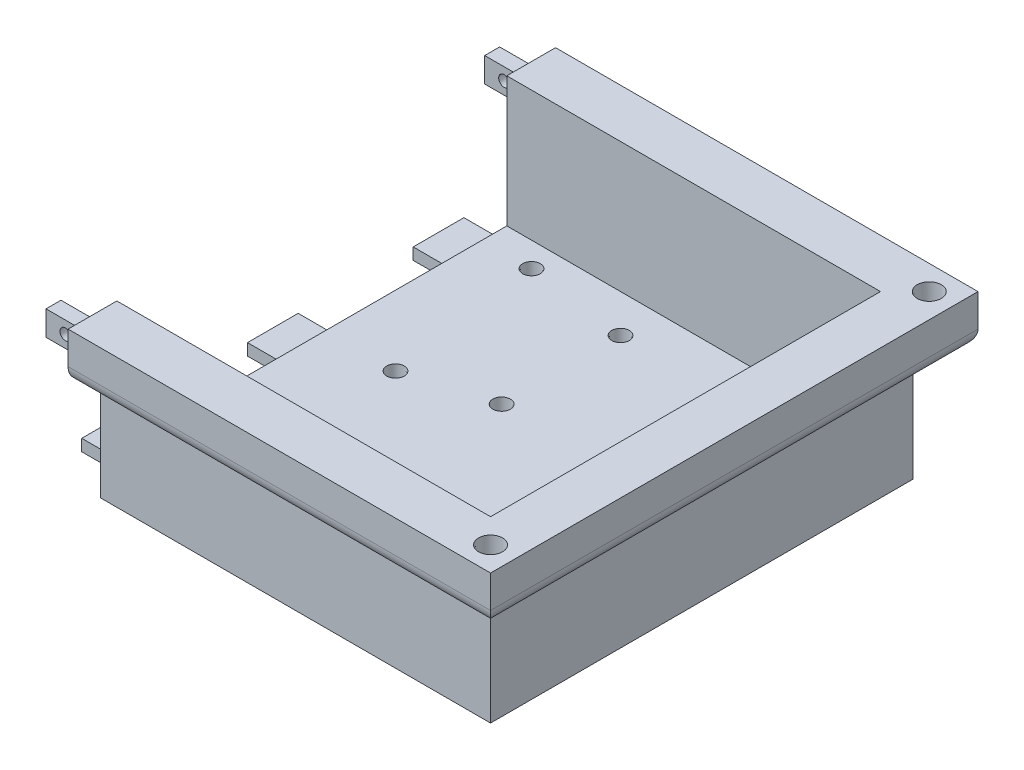
SolidWorks part; units mm, degrees
ref_plane "Front Plane" through (0, 0, 0) normal (0, 0, 1) x (1, 0, 0)
ref_plane "Top Plane" through (0, 0, 0) normal (0, 1, 0) x (1, 0, 0)
ref_plane "Right Plane" through (0, 0, 0) normal (1, 0, 0) x (0, 0, -1)
sketch "Sketch1" plane through (0, 0, 0) normal (0, 1, 0) x (1, 0, 0)
  line L1 (-102.5, 65) -> (102.5, 65)
  line L2 (-102.5, 65) -> (-102.5, -65)
  line L3 (-102.5, -65) -> (102.5, -65)
  line L4 (102.5, 65) -> (102.5, -65)
  line L5 (-102.5, 65) -> (102.5, -65) construction
  line L6 (-102.5, -65) -> (102.5, 65) construction
  point P0 (0, 0)
  dimension "D1" = 130
  dimension "D2" = 205
extrude "Boss-Extrude1" add sketch "Sketch1" along normal blind 10
sketch "Sketch2" plane through (0, 10, 0) normal (0, 1, 0) x (1, 0, 0)
  line L11 (-102.5, 65) -> (102.5, 65)
  line L12 (-102.5, 65) -> (-102.5, -65)
  line L13 (-102.5, -65) -> (102.5, -65)
  line L14 (-97.5, -60) -> (97.5, -60)
  line L15 (97.5, -60) -> (97.5, 60)
  line L16 (-97.5, 60) -> (-97.5, -60)
  line L17 (97.5, 60) -> (-97.5, 60)
  line L18 (-97.5, -60) -> (97.5, -60)
  line L19 (97.5, -60) -> (97.5, 60)
  line L20 (-97.5, 60) -> (-97.5, -60)
  line L21 (97.5, 60) -> (-97.5, 60)
  line L22 (102.5, 65) -> (102.5, -65)
  dimension "D1" = 5
extrude "Boss-Extrude2" add sketch "Sketch2" along normal blind 40
sketch "Sketch3" plane through (0, 10, 0) normal (0, 1, 0) x (1, 0, 0)
  line L0 (-97.5, -60) -> (97.5, -60) construction
  line L1 (-92.5, -55) -> (-2.5, -55)
  line L2 (-92.5, -55) -> (-92.5, -2)
  line L3 (-92.5, -2) -> (-2.5, -2)
  line L4 (-2.5, -55) -> (-2.5, -2)
  line L5 (-84.35, -28.5) -> (-10.65, -28.5) construction
  line L6 (2.5, -2) -> (2.5, -55)
  line L7 (2.5, -55) -> (92.5, -55)
  line L8 (92.5, -55) -> (92.5, -2)
  line L9 (92.5, -2) -> (2.5, -2)
  line L10 (-97.5, 60) -> (-97.5, -60) construction
  line L13 (10.65, -28.5) -> (84.35, -28.5) construction
  circle A0 centre (-84.35, -28.5) radius 2.5
  circle A1 centre (-10.65, -28.5) radius 2.5
  point P4 (-47.5, -2)
  point P12 (-47.5, -28.5)
  point P13 (-92.5, -28.5)
  point P17 (84.35, -28.5)
  point P21 (10.65, -28.5)
  point P25 (2.5, -28.5)
  point P26 (47.5, -2)
  point P27 (47.5, -28.5)
  dimension "D5" = 5
  dimension "D1" = 90
  dimension "D2" = 53
  dimension "D3" = 5
  dimension "D4" = 73.7
  dimension "D6" = 90
  dimension "D7" = 53
  dimension "D8" = 5
  dimension "D9" = 5
  dimension "D10" = 73.7
sketch "Sketch6" plane through (-102.5, 0, 0) normal (-1, 0, 0) x (0, 0, 1)
  line L0 (-65, 50) -> (65, 50) construction
  line L1 (-60, 50) -> (0, 50)
  line L2 (-60, 50) -> (-60, 10)
  line L3 (-60, 10) -> (0, 10)
  line L4 (0, 50) -> (0, 10)
  line L5 (-60, 10) -> (60, 10) construction
extrude "Cut-Extrude1" cut sketch "Sketch6" against normal up to next
sketch "Sketch10" plane through (0, 10, 0) normal (0, 1, 0) x (1, 0, 0)
  line L1 (26, 51.5) -> (69, 51.5)
  line L2 (26, 51.5) -> (26, 8.5)
  line L3 (26, 8.5) -> (69, 8.5)
  line L4 (69, 51.5) -> (69, 8.5)
  line L6 (29.2, 48.3) -> (65.8, 48.3) construction
  line L7 (65.8, 48.3) -> (65.8, 11.7) construction
  line L8 (65.8, 11.7) -> (29.2, 11.7) construction
  line L9 (29.2, 11.7) -> (29.2, 48.3) construction
  line L12 (92.5, -2) -> (2.5, -2) construction
  line L13 (-102.5, 60) -> (-102.5, 0) construction
  point P8 (29.2, 48.3)
  point P9 (65.8, 48.3)
  point P10 (29.2, 11.7)
  point P11 (65.8, 11.7)
  point P14 (47.5, 48.3)
  point P17 (47.5, 8.5)
  point P18 (29.2, 30)
  point P19 (26, 30)
  point P20 (47.5, -2)
  point P21 (-102.5, 30)
  dimension "D1" = 43
  dimension "D2" = 43
  dimension "D5" = 36.6
sketch "Sketch9" plane through (0, 10, 0) normal (0, 1, 0) x (1, 0, 0)
  line L1 (-92.5, 55) -> (9.1, 55)
  line L2 (-92.5, 55) -> (-92.5, 1.7)
  line L3 (-92.5, 1.7) -> (9.1, 1.7)
  line L4 (9.1, 55) -> (9.1, 1.7)
  line L5 (97.5, 60) -> (-102.5, 60) construction
  line L7 (-97.5, 0) -> (-97.5, -60) construction
  point P8 (4.05, 4.2)
  point P9 (-26.4, 9.3)
  point P10 (-26.4, 37.2)
  point P11 (-2.3, 52.4)
  point P12 (-77.2, 52.4)
  point P13 (-78.5, 4.2)
  dimension "D1" = 101.6
  dimension "D2" = 53.3
  dimension "D3" = 5
  dimension "D4" = 2.5
  dimension "D5" = 14
  dimension "D6" = 1.3
  dimension "D7" = 50.8
  dimension "D8" = 24.1
  dimension "D9" = 27.9
  dimension "D10" = 15.2
  dimension "D11" = 5.1
  dimension "D12" = 82.55
  dimension "D13" = 5
hole_wizard "Hole1" positions "Sketch7" profile "Sketch8" legacy
sketch "Sketch7" plane through (0, 10, 0) normal (0, 1, 0) x (1, 0, 0)
  point P0 (-84.35, -28.5)
  point P3 (-10.65, -28.5)
  point P6 (-78.5, 4.2)
  point P9 (-77.2, 52.4)
  point P12 (-26.4, 9.3)
  point P15 (-26.4, 37.2)
  point P18 (-2.3, 52.4)
  point P21 (4.05, 4.2)
  point P25 (29.2, 48.3)
  point P28 (65.8, 48.3)
  point P31 (65.8, 11.7)
  point P34 (29.2, 11.7)
  point P38 (10.65, -28.5)
  point P41 (84.35, -28.5)
sketch "Sketch8" plane through (-84.35, 10, 28.5) normal (1, 0, 0) x (0, 0, 1)
  line L0 (0, 0) -> (0, 8)
  line L1 (0, 8) -> (2.4, 8)
  line L2 (2.4, 8) -> (2.4, 6)
  line L3 (2.4, 6) -> (2.7, 6)
  line L4 (2.7, 6) -> (2.7, 0)
  line L5 (2.7, 0) -> (0, 0)
  line L6 (0, 110) -> (0, -10) construction
  dimension "Diameter" = 4.8
  dimension "Depth" = 8
  dimension "C-Bore Diameter" = 5.4
  dimension "C-Bore Depth" = 6
chamfer "Chamfer1" distance 6 distance2 0.3 14 edges at (-84.35, 4, 31.2) (-10.65, 4, 31.2) (-2.3, 4, -49.7) (4.05, 4, -1.5) (-26.4, 4, -6.6) (-26.4, 4, -34.5) (-77.2, 4, -49.7) (-78.5, 4, -1.5) (65.8, 4, -45.6) (29.2, 4, -45.6) (29.2, 4, -9) (65.8, 4, -9) (84.35, 4, 31.2) (10.65, 4, 31.2) first distance on face at (-84.35, 4, 31.2) first distance on face at (-10.65, 4, 31.2) first distance on face at (-2.3, 4, -49.7) first distance on face at (4.05, 4, -1.5) first distance on face at (-26.4, 4, -6.6) first distance on face at (-26.4, 4, -34.5) first distance on face at (-77.2, 4, -49.7) first distance on face at (-78.5, 4, -1.5) first distance on face at (65.8, 4, -45.6) first distance on face at (29.2, 4, -45.6) first distance on face at (29.2, 4, -9) first distance on face at (65.8, 4, -9) first distance on face at (84.35, 4, 31.2) first distance on face at (10.65, 4, 31.2)
sketch "Sketch11" plane through (0, 50, 0) normal (0, 1, 0) x (1, 0, 0)
  line L0 (-112.5, 75) -> (112.5, 75)
  line L1 (112.5, 75) -> (112.5, -75)
  line L2 (112.5, -75) -> (-112.5, -75)
  line L3 (-112.5, -75) -> (-112.5, 0)
  line L4 (-112.5, 0) -> (-102.5, 0)
  line L5 (-102.5, 0) -> (-102.5, -65)
  line L6 (-102.5, -65) -> (102.5, -65)
  line L7 (102.5, -65) -> (102.5, 65)
  line L9 (-112.5, 60) -> (-112.5, 75)
  line L11 (-102.5, 60) -> (-112.5, 60)
  line L12 (-102.5, 60) -> (-102.5, 65)
  line L13 (-102.5, 65) -> (102.5, 65)
  dimension "D1" = 10
  dimension "D2" = 10
  dimension "D3" = 10
  dimension "D4" = 10
  dimension "D5" = 10
extrude "Boss-Extrude3" add sketch "Sketch11" against normal blind 15
fillet "Fillet1" radius 5 9 edges at (-112.5, 35, 37.5) (0, 35, 75) (112.5, 35, 0) (0, 35, -75) (-102.5, 35, -62.5) (0, 35, -65) (102.5, 35, 0) (-102.5, 35, 32.5) (0, 35, 65)
hole_wizard "Hole2" positions "Sketch12" profile "Sketch13" legacy
sketch "Sketch12" plane through (0, 50, 0) normal (0, 1, 0) x (1, 0, 0)
  line L0 (-112.5, 75) -> (-112.5, 60) construction
  line L1 (-97.5, 0) -> (-112.5, 0) construction
  line L3 (-97.5, -60) -> (-97.5, -75) construction
  line L4 (-112.5, -75) -> (112.5, -75) construction
  line L6 (97.5, -60) -> (112.5, -60) construction
  line L7 (112.5, -75) -> (112.5, 75) construction
  point P0 (-105, 67.5)
  point P2 (105, 67.5)
  point P4 (105, -67.5)
  point P6 (-105, -67.5)
  point P11 (-112.5, 67.5)
  point P18 (-105, 0)
  point P27 (-97.5, -67.5)
  point P37 (105, -60)
sketch "Sketch13" plane through (-105, 50, -67.5) normal (1, 0, 0) x (0, 0, 1)
  line L0 (0, 0) -> (0, 10)
  line L1 (0, 10) -> (3.4, 10)
  line L2 (3.4, 10) -> (3.4, 6)
  line L3 (3.4, 6) -> (3.7, 6)
  line L4 (3.7, 6) -> (3.7, 0)
  line L5 (3.7, 0) -> (0, 0)
  line L6 (0, 110) -> (0, -10) construction
  dimension "Diameter" = 6.8
  dimension "Depth" = 10
  dimension "C-Bore Diameter" = 7.4
  dimension "C-Bore Depth" = 6
chamfer "Chamfer2" distance 6 distance2 0.3 4 edges at (-105, 44, 71.2) (105, 44, 71.2) (105, 44, -63.8) (-105, 44, -63.8) first distance on face at (-105, 44, 71.2) first distance on face at (105, 44, 71.2) first distance on face at (105, 44, -63.8) first distance on face at (-105, 44, -63.8)
ref_plane "Plane1" through (-17.5, 0, 0) normal (-1, 0, 0) x (0, 0, 1)
sketch "Sketch14" plane through (-17.5, 0, 0) normal (-1, 0, 0) x (0, 0, 1)
  line L1 (-91.5308, -9.5982) -> (88.055, -9.5982)
  line L2 (-91.5308, -9.5982) -> (-91.5308, 62.5672)
  line L3 (-91.5308, 62.5672) -> (88.055, 62.5672)
  line L4 (88.055, -9.5982) -> (88.055, 62.5672)
extrude "Cut-Extrude2" cut sketch "Sketch14" along normal blind 150 contours L2 L1 L4 L3
sketch "Sketch15" plane through (-17.5, 0, 0) normal (-1, 0, 0) x (0, 0, 1)
  line L0 (60, 10) -> (60, 0) construction
  line L1 (-58.8, 6.8) -> (-43.2, 6.8)
  line L2 (-58.8, 6.8) -> (-58.8, 3.2)
  line L3 (-58.8, 3.2) -> (-43.2, 3.2)
  line L4 (-43.2, 6.8) -> (-43.2, 3.2)
  line L5 (43.2, 6.8) -> (58.8, 6.8)
  line L6 (43.2, 6.8) -> (43.2, 3.2)
  line L7 (43.2, 3.2) -> (58.8, 3.2)
  line L8 (58.8, 6.8) -> (58.8, 3.2)
  line L9 (-7.8, 6.8) -> (7.8, 6.8)
  line L10 (-7.8, 6.8) -> (-7.8, 3.2)
  line L11 (-7.8, 3.2) -> (7.8, 3.2)
  line L12 (7.8, 6.8) -> (7.8, 3.2)
  line L13 (-65, 0) -> (65, 0) construction
  line L15 (-69.8, 46.8) -> (-65.2, 46.8)
  line L16 (-69.8, 46.8) -> (-69.8, 39.2)
  line L17 (-69.8, 39.2) -> (-65.2, 39.2)
  line L18 (-65.2, 46.8) -> (-65.2, 39.2)
  line L19 (65.2, 46.8) -> (69.8, 46.8)
  line L20 (65.2, 46.8) -> (65.2, 39.2)
  line L21 (65.2, 39.2) -> (69.8, 39.2)
  line L22 (69.8, 46.8) -> (69.8, 39.2)
  line L23 (-75, 50) -> (-60, 50) construction
  line L24 (60, 50) -> (75, 50) construction
  point P12 (0, 3.2)
  point P20 (60, 5)
  point P21 (-58.8, 5)
  point P30 (0, 0)
  point P31 (0, 0)
  point P32 (-67.5, 50)
  point P35 (-67.5, 46.8)
  point P38 (67.5, 50)
  point P39 (67.5, 46.8)
  dimension "D1" = 3.6
  dimension "D2" = 15.6
  dimension "D3" = 35.4
  dimension "D4" = 35.4
  dimension "D5" = 7.6
  dimension "D6" = 4.6
  dimension "D7" = 3.2
extrude "Boss-Extrude4" add sketch "Sketch15" along normal blind 12
hole_wizard "M3 Clearance Hole1" positions "Sketch16" profile "Sketch17" hole size "M3" standard "ANSI Metric" end condition through all
sketch "Sketch16" plane through (0, 0, -65.2) normal (0, 0, 1) x (1, 0, 0)
  line L0 (-29.5, 39.2) -> (-29.5, 46.8) construction
  line L1 (-29.5, 46.8) -> (-17.5, 46.8) construction
  point P0 (-23.5, 43)
  point P5 (-29.5, 43)
  point P8 (-23.5, 46.8)
sketch "Sketch17" plane through (-23.5, 43, -65.2) normal (1, 0, 0) x (0, -1, 0)
  line L0 (0, 0) -> (0, 9.8)
  line L1 (0, 9.8) -> (1.7, 9.8)
  line L2 (1.7, 9.8) -> (1.7, 0)
  line L5 (1.7, 0) -> (0, 0)
  line L11 (0, -6.35) -> (0, 107.95) construction
  dimension "Thru Hole Dia." = 3.4
  dimension "Thru Hole Depth" = 9.8
mirror "Mirror1" about plane through (0, 0, 0) normal (0, 0, 1) of "M3 Clearance Hole1"
